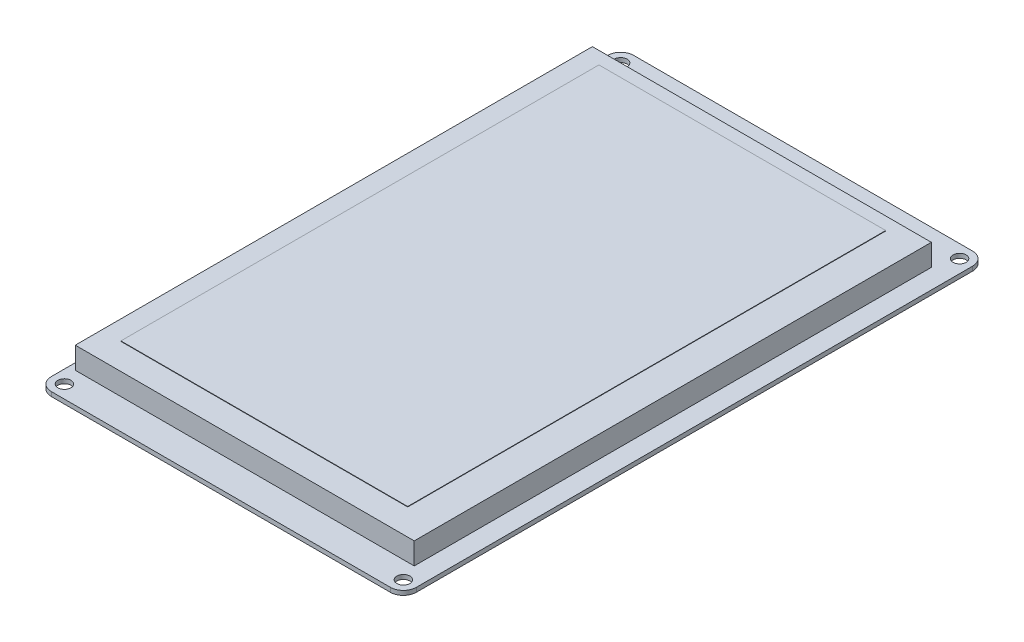
SolidWorks part; units mm, degrees
ref_plane "Front Plane" through (0, 0, 0) normal (0, 0, 1) x (1, 0, 0)
ref_plane "Top Plane" through (0, 0, 0) normal (0, 1, 0) x (1, 0, 0)
ref_plane "Right Plane" through (0, 0, 0) normal (1, 0, 0) x (0, 0, -1)
sketch "Sketch1" plane through (0, 0, 0) normal (0, 1, 0) x (1, 0, 0)
  line L1 (-39, 56.863) -> (39, 56.863)
  line L2 (-42, 53.863) -> (-42, -74.137)
  line L3 (-39, -77.137) -> (39, -77.137)
  line L4 (42, 53.863) -> (42, -74.137)
  line L5 (-40.5, 48.863) -> (37.5, 48.863)
  line L6 (-40.5, 48.863) -> (-40.5, -70.137)
  line L7 (-40.5, -70.137) -> (37.5, -70.137)
  line L8 (37.5, 48.863) -> (37.5, -70.137)
  circle A0 centre (-39, 53.863) radius 1.5
  circle A1 centre (39, 53.863) radius 1.5
  circle A2 centre (-39, -74.137) radius 1.5
  circle A3 centre (39, -74.137) radius 1.5
  arc A4 (39, -77.137) -> (42, -74.137) centre (39, -74.137) ccw
  arc A5 (-42, -74.137) -> (-39, -77.137) centre (-39, -74.137) ccw
  arc A6 (39, 56.863) -> (42, 53.863) centre (39, 53.863) cw
  arc A7 (-39, 56.863) -> (-42, 53.863) centre (-39, 53.863) ccw
  point P0 (0, 0)
  point P16 (42, -77.137)
  point P21 (42, 56.863)
  point P24 (-42, 56.863)
  dimension "D3" = 3
  dimension "D4" = 3
  dimension "D1" = 84
  dimension "D2" = 134
  dimension "D5" = 78
  dimension "D6" = 119
  dimension "D7" = 4.5
  dimension "D8" = 8
extrude "Boss-Extrude1" add sketch "Sketch1" along normal blind 6 contours L8 L5 L6 L7 region at (-1.5, 0, 10.637)
extrude "Boss-Extrude2" add sketch "Sketch1<3>" along normal blind 1
sketch "Sketch1<3>" plane through (0, 0, 0) normal (0, 1, 0) x (1, 0, 0) same geometry as "Sketch1"
sketch "Sketch2" plane through (0, 6, 0) normal (0, 1, 0) x (1, 0, 0)
  line L0 (37.5, 48.863) -> (37.5, -70.137) construction
  line L1 (-36, 45.863) -> (30, 45.863)
  line L2 (-36, 45.863) -> (-36, -64.137)
  line L3 (-36, -64.137) -> (30, -64.137)
  line L4 (30, 45.863) -> (30, -64.137)
  line L5 (-40.5, 48.863) -> (37.5, 48.863) construction
  dimension "D1" = 7.5
  dimension "D2" = 3
  dimension "D3" = 110
  dimension "D4" = 66
extrude "Boss-Extrude3" add sketch "Sketch2" along normal blind 0.1
